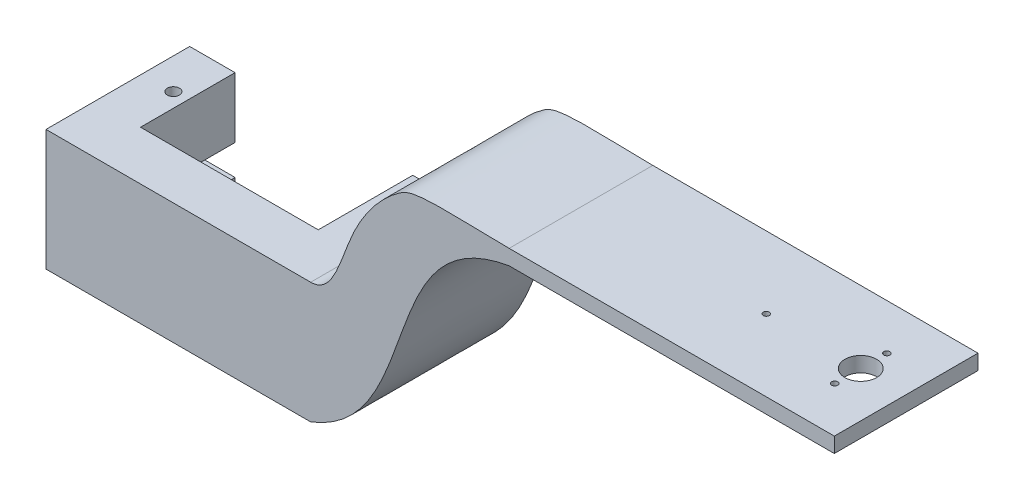
SolidWorks part; units mm, degrees
material "ABS"
ref_plane "Front Plane" through (0, 0, 0) normal (0, 0, 1) x (1, 0, 0)
ref_plane "Top Plane" through (0, 0, 0) normal (0, 1, 0) x (1, 0, 0)
ref_plane "Right Plane" through (0, 0, 0) normal (1, 0, 0) x (0, 0, -1)
sketch "Sketch1" plane through (0, 0, 0) normal (0, 1, 0) x (1, 0, 0)
  line L1 (-10, -9.5) -> (-45, -9.5)
  line L2 (-10, -9.5) -> (-10, 9.5)
  line L3 (-10, 9.5) -> (-45, 9.5)
  line L4 (-45, -9.5) -> (-45, 9.5)
  line L5 (-10, -9.5) -> (-45, 9.5) construction
  line L6 (-10, 9.5) -> (-45, -9.5) construction
  line L8 (-55, 0) -> (55, 0) construction
  line L9 (0, -55) -> (0, 55) construction
  point P0 (-27.5, 0)
  dimension "D1" = 35
  dimension "D2" = 19
  dimension "D3" = 45
extrude "Boss-Extrude1" add sketch "Sketch1" along normal blind 2
sketch "Sketch2" plane through (0, 0, 0) normal (0, -1, 0) x (-1, 0, 0)
  line L0 (10, 9.5) -> (45, 9.5) construction
  line L1 (45, -9.5) -> (10, -9.5)
  line L2 (45, -9.5) -> (45, 9.5)
  line L3 (45, 9.5) -> (10, 9.5)
  line L4 (10, -9.5) -> (10, 9.5)
  dimension "D1" = 35
extrude "Boss-Extrude2" add sketch "Sketch2" along normal blind 14
sketch "Sketch5" plane through (0, 2, 0) normal (0, 1, 0) x (1, 0, 0)
  line L1 (-15.5, -3) -> (-39, -3)
  line L2 (-15.5, -3) -> (-15.5, 9.5)
  line L3 (-15.5, 9.5) -> (-39, 9.5)
  line L4 (-39, -3) -> (-39, 9.5)
  line L5 (-15.5, -3) -> (-39, 9.5) construction
  line L6 (-15.5, 9.5) -> (-39, -3) construction
  line L7 (-45, 9.5) -> (-45, -9.5) construction
  line L8 (-10, 9.5) -> (-45, 9.5) construction
  point P0 (-27.25, 3.25)
  point P5 (-27.25, 3.1577)
  point P9 (0, 0)
  point P10 (-27.25, 0)
  point P11 (0, 0)
  dimension "D1" = 23.5
  dimension "D2" = 6
  dimension "D3" = 12.5
extrude "Cut-Extrude1" cut sketch "Sketch5" against normal blind 16
sketch "Sketch6" plane through (-15.5, 0, 0) normal (-1, 0, 0) x (0, 0, 1)
  line L1 (-10.7236, -6) -> (1.2764, -6)
  line L2 (-10.7236, -6) -> (-10.7236, -10)
  line L3 (-10.7236, -10) -> (1.2764, -10)
  line L4 (1.2764, -6) -> (1.2764, -10)
  line L5 (-10.7236, -6) -> (1.2764, -10) construction
  line L6 (-10.7236, -10) -> (1.2764, -6) construction
  line L7 (-9.5, -14) -> (3, -14) construction
  point P0 (-4.7236, -8)
  point P7 (0, 0)
  point P8 (-2.9591, -8)
  point P9 (-3.2389, -8)
  point P10 (-3.2236, -8)
  dimension "D1" = 12
  dimension "D2" = 4
  dimension "D3" = 4
extrude "Cut-Extrude2" cut sketch "Sketch6" along normal blind 35
sketch "Sketch7" plane through (0, 2, 0) normal (0, 1, 0) x (1, 0, 0)
  line L1 (-15.5, -3) -> (-15.5, 9.5) construction
  line L6 (-10, 9.5) -> (-15.5, 9.5) construction
  circle A0 centre (-40.9, 3.25) radius 0.8
  circle A1 centre (-13.6, 3.25) radius 0.8
  point P2 (-13.6, 3.5261)
  point P3 (-13.6, 2.6695)
  point P8 (0, 0)
  point P9 (-13.6, 2.7655)
  point P10 (0, 0)
  point P11 (-13.6, 0)
  point P12 (-13.6, 0)
  point P13 (-13.6, 0)
  point P14 (0, 0)
  point P15 (-13.6, 0)
  point P16 (-40.9, 0)
  point P17 (0, 0)
  point P18 (-13.6, 0)
  point P19 (0, 0)
  point P20 (0, 0)
  dimension "D1" = 27.3
  dimension "D2" = 1.9
  dimension "D3" = 6.25
sketch "Sketch10" plane through (0, -14, 0) normal (0, -1, 0) x (-1, 0, 0)
  line L0 (-1.1, 0) -> (1.1, 0) construction
  circle A1 centre (42.4267, 7.2921) radius 0.7139
  circle A2 centre (12.8504, 7.2921) radius 0.7139
  circle A4 centre (12.8504, -7.2921) radius 0.7139
  circle A5 centre (42.4267, -7.2921) radius 0.7139
sketch "Sketch15" plane through (0, 0, 9.5) normal (0, 0, 1) x (1, 0, 0)
  line L0 (-45, 2) -> (-10, 2) construction
  line L1 (16.2443, 17) -> (16.2443, 19)
  line L2 (-10, 2) -> (-10, -14)
  spline S0 degree 3 poles (-10, -14) (5.2157, -8.0829) (-1.5717, 13.9677) (16.2443, 17) knots 0 0 0 0 1 1 1 1
  spline S1 degree 3 poles (16.2443, 19) (11.2126, 19) (4.0665, 19.5532) (-0.1068, 16.9833) (-5.2423, 11.0378) (-6.9778, 2) (-10, 2) knots 0 0 0 0 0.246138 0.311425 0.652874 1 1 1 1
  dimension "D1" = 15
  dimension "D2" = 2
extrude "Boss-Extrude7" add sketch "Sketch15" against normal blind 19
sketch "Sketch17" plane through (16.2443, 0, 0) normal (1, 0, 0) x (0, 0, -1)
  line L1 (9.5, 19) -> (-9.5, 19)
  line L2 (9.5, 19) -> (9.5, 17)
  line L3 (9.5, 17) -> (-9.5, 17)
  line L4 (-9.5, 19) -> (-9.5, 17)
extrude "Boss-Extrude8" add sketch "Sketch17" along normal blind 40
extrude "Boss-Extrude9" add sketch "Sketch10" along normal blind 0.5
fillet "Fillet2" radius 0.5 4 edges at (-12.8504, -14.5, -8.006) (-12.8504, -14.5, 8.006) (-42.4267, -14.5, -8.006) (-42.4267, -14.5, 8.006)
sketch "Sketch18" plane through (0, 19, 0) normal (0, 1, 0) x (1, 0, 0)
  line L0 (-8.8, 0) -> (8.8, 0) construction
  line L1 (56.2443, 9.5) -> (56.2443, -9.5) construction
  circle A0 centre (53.2443, 3.45) radius 0.4
  circle A2 centre (53.2443, -3.45) radius 0.4
  circle A3 centre (50.2148, 25.8517) radius 0.4
  circle A4 centre (40.7443, 0) radius 0.4
  dimension "D1" = 6.9
  dimension "D2" = 12.5
  dimension "D3" = 3
extrude "Cut-Extrude6" cut sketch "Sketch18" against normal blind 10.5
sketch "Sketch19" plane through (0, 19, 0) normal (0, 1, 0) x (1, 0, 0)
  line L0 (-8.8, 0) -> (8.8, 0) construction
  line L1 (56.2443, 9.5) -> (56.2443, -9.5) construction
  circle A0 centre (53.2443, 0) radius 2.1
  dimension "D1" = 3
extrude "Cut-Extrude7" cut sketch "Sketch19" against normal blind 10.5
sketch "Sketch20" plane through (56.2443, 0, 0) normal (1, 0, 0) x (0, 0, -1)
  line L1 (9.5, 19) -> (-9.5, 19)
  line L2 (9.5, 19) -> (9.5, 17)
  line L3 (9.5, 17) -> (-9.5, 17)
  line L4 (-9.5, 19) -> (-9.5, 17)
extrude "Boss-Extrude10" add sketch "Sketch20" along normal blind 3
extrude "Cut-Extrude8" cut sketch "Sketch7" against normal blind 8
